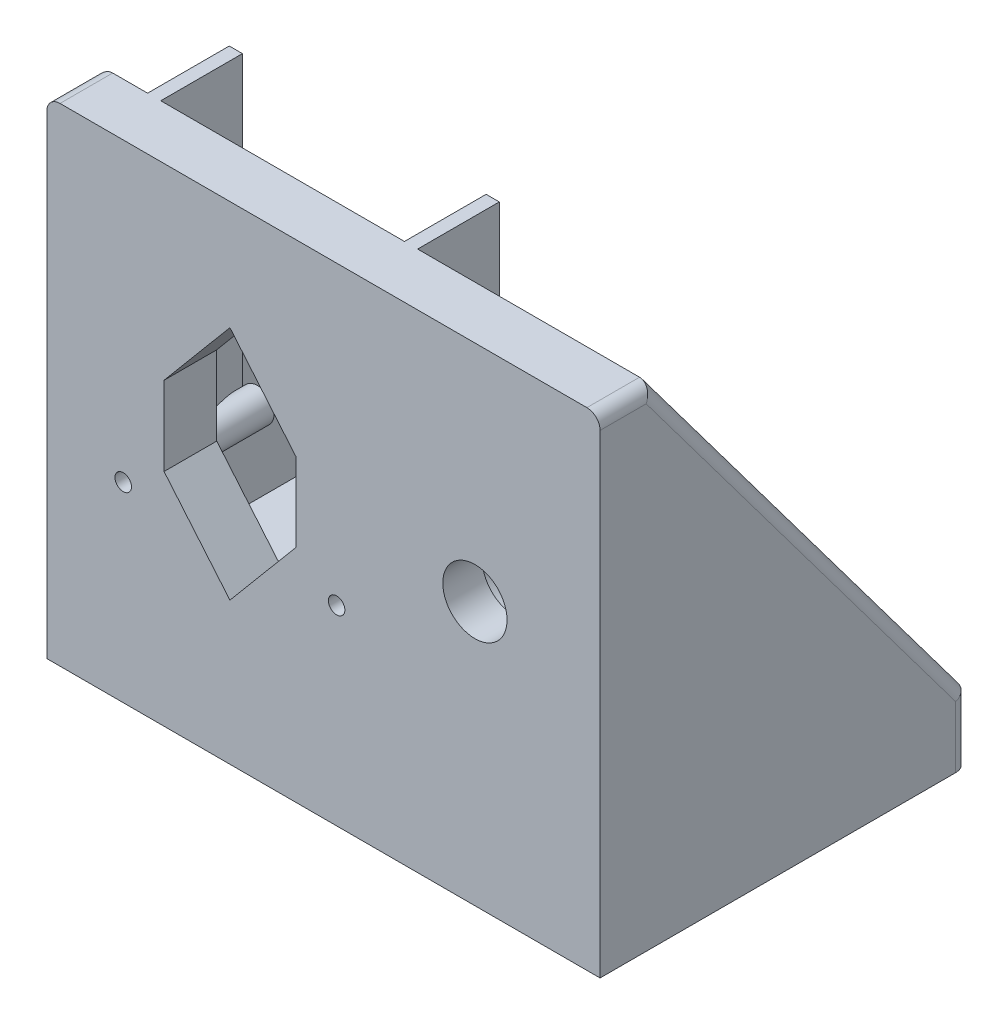
SolidWorks part; units mm, degrees
ref_plane "Front Plane" through (0, 0, 0) normal (0, 0, 1) x (1, 0, 0)
ref_plane "Top Plane" through (0, 0, 0) normal (0, 1, 0) x (1, 0, 0)
ref_plane "Right Plane" through (0, 0, 0) normal (1, 0, 0) x (0, 0, -1)
sketch "Sketch1" plane through (0, 0, 0) normal (0, 1, 0) x (1, 0, 0)
  line L1 (0, 0) -> (42, 0)
  line L2 (0, 0) -> (0, 28)
  line L3 (0, 28) -> (42, 28)
  line L4 (42, 0) -> (42, 28)
  dimension "D1" = 28
  dimension "D2" = 42
extrude "Boss-Extrude1" add sketch "Sketch1" along normal blind 5
sketch "Sketch2" plane through (0, 5, 0) normal (0, 1, 0) x (1, 0, 0)
  line L0 (42, 0) -> (42, 28) construction
  line L1 (0, 0) -> (42, 0)
  line L2 (0, 0) -> (0, 4)
  line L3 (0, 4) -> (42, 4)
  line L4 (42, 0) -> (42, 4)
  dimension "D1" = 4
extrude "Boss-Extrude2" add sketch "Sketch2" along normal blind 32
hole_wizard "Tap Drill for M1.6x0.35 Tap1" positions "Sketch3" profile "Sketch4" hole size "M1.6x0.35" standard "ANSI Metric" end condition through all
sketch "Sketch3" plane through (0, 0, -4) normal (0, 0, -1) x (-1, 0, 0)
  line L4 (0, 37) -> (0, 5) construction
  line L5 (-5.8, 14.5) -> (-22, 14.5) construction
  line L6 (-42, 37) -> (0, 37) construction
  point P0 (-22, 14.5)
  point P2 (-5.8, 14.5)
  dimension "D1" = 22.5
  dimension "D2" = 22
  dimension "D3" = 16.2
sketch "Sketch4" plane through (22, 14.5, -4) normal (1, 0, 0) x (0, 1, 0)
  line L0 (0, 0) -> (0, 4)
  line L1 (0, 4) -> (0.625, 4)
  line L2 (0.625, 4) -> (0.625, 0)
  line L5 (0.625, 0) -> (0, 0)
  line L11 (0, -6.35) -> (0, 107.95) construction
  dimension "Thru Hole Dia." = 1.25
  dimension "Thru Hole Depth" = 4
hole_wizard "M3 Clearance Hole1" positions "Sketch5" profile "Sketch6" hole size "M3" standard "ANSI Metric" end condition through all
sketch "Sketch5" plane through (0, 5, 0) normal (0, 1, 0) x (1, 0, 0)
  line L1 (15.5, 23) -> (30.5, 23) construction
  line L2 (15.5, 23) -> (15.5, 10) construction
  line L3 (15.5, 10) -> (30.5, 10) construction
  line L4 (30.5, 23) -> (30.5, 10) construction
  line L9 (23, 28) -> (23, 23) construction
  line L12 (30.5, 16.5) -> (38, 16.5) construction
  line L15 (0, 0) -> (42, 0) construction
  line L16 (42, 4) -> (42, 28) construction
  point P0 (15.5, 23)
  point P2 (30.5, 23)
  point P4 (30.5, 10)
  point P6 (15.5, 10)
  dimension "D1" = 15
  dimension "D2" = 13
  dimension "D3" = 23
  dimension "D4" = 11.5
sketch "Sketch6" plane through (15.5, 5, -23) normal (1, 0, 0) x (0, 0, 1)
  line L0 (0, 0) -> (0, 5)
  line L1 (0, 5) -> (1.7, 5)
  line L2 (1.7, 5) -> (1.7, 0)
  line L5 (1.7, 0) -> (0, 0)
  line L11 (0, -6.35) -> (0, 107.95) construction
  dimension "Thru Hole Dia." = 3.4
  dimension "Thru Hole Depth" = 5
sketch "Sketch7" plane through (0, 0, 0) normal (-1, 0, 0) x (0, 0, 1)
  line L0 (-28, 5) -> (-4, 37)
  line L1 (-4, 37) -> (-4, 5)
  line L2 (-4, 5) -> (-28, 5)
extrude "Boss-Extrude3" add sketch "Sketch7" against normal blind 2.5
sketch "Sketch8" plane through (42, 0, 0) normal (1, 0, 0) x (0, 0, -1)
  line L0 (28, 5) -> (4, 37)
  line L1 (4, 37) -> (4, 5)
  line L2 (4, 5) -> (28, 5)
extrude "Boss-Extrude4" add sketch "Sketch8" against normal blind 2.5
fillet "Fillet2" radius 1 8 edges at (39.5, 21, -16) (2.5, 21, -16) (42, 37, -2) (0, 37, -2) (0, 2.5, -28) (42, 2.5, -28) (42, 21, -16) (0, 21, -16)
sketch "Sketch9" plane through (0, 0, -4) normal (0, 0, -1) x (-1, 0, 0)
  line L0 (-42, 36) -> (-42, 0) construction
  line L3 (-39.5, 5) -> (-2.5, 5) construction
  circle A0 centre (-32.5, 20) radius 3.25
  dimension "D1" = 6.5
  dimension "D2" = 9.5
  dimension "D3" = 15
extrude "Cut-Extrude1" cut sketch "Sketch9" against normal blind 1
sketch "Sketch10" plane through (0, 0, -3) normal (0, 0, -1) x (-1, 0, 0)
  circle A0 centre (-32.5, 20) radius 2.44
  dimension "D1" = 4.88
extrude "Cut-Extrude2" cut sketch "Sketch10" against normal through all
sketch "Sketch11" plane through (0, 0, -4) normal (0, 0, -1) x (-1, 0, 0)
  line L0 (-22, 14.5) -> (-5.8, 14.5) construction
  line L1 (-13.9, 14.5) -> (-13.9, 37) construction
  line L2 (-40.5, 37) -> (-1.5, 37) construction
  line L3 (-3.65, 37) -> (-4.65, 37)
  line L8 (-24.15, 37) -> (-23.15, 37)
  line L9 (-24.15, 37) -> (-24.15, 14.0101)
  line L11 (-23.15, 37) -> (-23.15, 14.9899)
  line L12 (-3.65, 37) -> (-3.65, 14.0101)
  line L13 (-3.65, 14.0101) -> (-4.65, 14.0101)
  line L14 (-4.65, 37) -> (-4.65, 14.9899)
  line L15 (-24.15, 14.0101) -> (-23.15, 14.0101)
  arc A0 (-23.15, 14.0101) -> (-23.15, 14.9899) centre (-22, 14.5) ccw
  arc A1 (-4.65, 14.9899) -> (-4.65, 14.0101) centre (-5.8, 14.5) ccw
  circle A2 centre (-5.8, 14.5) radius 0.625 construction
  circle A3 centre (-5.8, 14.5) radius 0.625
  circle A4 centre (-22, 14.5) radius 0.625 construction
  circle A5 centre (-22, 14.5) radius 0.625
  point P25 (-24.15, 25.5051)
  dimension "D1" = 2.5
  dimension "D2" = 1
  dimension "D3" = 1
  dimension "D4" = 20.5
extrude "Boss-Extrude5" add sketch "Sketch11" along normal blind 6.2
sketch "Sketch12" plane through (0, 0, -4) normal (0, 0, -1) x (-1, 0, 0)
  line L0 (-5.8, 14.5) -> (-22, 14.5) construction
  line L1 (-11.4, 18) -> (-16.4, 18)
  line L2 (-11.4, 18) -> (-11.4, 21.5)
  line L3 (-11.4, 21.5) -> (-16.4, 21.5)
  line L4 (-16.4, 18) -> (-16.4, 21.5)
  line L5 (-13.9, 14.5) -> (-13.9, 18) construction
  circle A0 centre (-5.8, 14.5) radius 0.625 construction
  dimension "D1" = 3.5
  dimension "D2" = 5
  dimension "D3" = 3.5
sketch "Sketch13" plane through (0, 0, -4) normal (0, 0, -1) x (-1, 0, 0)
  line L1 (-13.9, 28.7088) -> (-8.9, 22.75)
  line L3 (-13.9, 14.5) -> (-13.9, 28.7088) construction
  line L4 (-8.9, 22.75) -> (-8.9, 16.75)
  line L5 (-8.9, 16.75) -> (-13.9, 10.7912)
  line L6 (-13.9, 10.7912) -> (-18.9, 16.75)
  line L7 (-18.9, 16.75) -> (-18.9, 22.75)
  line L8 (-11.4, 18) -> (-11.4, 21.5) construction
  line L9 (-11.4, 18) -> (-11.4, 21.5) construction
  line L10 (-8.9, 19.75) -> (-11.4, 19.75) construction
  line L11 (-8.9, 16.75) -> (-18.9, 16.75) construction
  line L12 (-18.9, 22.75) -> (-13.9, 28.7088)
  line L13 (-8.9, 22.75) -> (-18.9, 22.75) construction
  dimension "D1" = 40
  dimension "D2" = 6
  dimension "D3" = 10
extrude "Cut-Extrude3" cut sketch "Sketch13" against normal through all
sketch "Sketch14" plane through (0, 37, 0) normal (0, 1, 0) x (1, 0, 0)
  line L0 (23.15, 10.2) -> (21.15, 4)
  line L1 (23.15, 4) -> (4.65, 4) construction
  line L2 (21.15, 4) -> (23.15, 4)
  line L3 (23.15, 4) -> (23.15, 10.2)
  line L4 (4.65, 10.2) -> (6.65, 4)
  line L5 (6.65, 4) -> (4.65, 4)
  line L6 (4.65, 4) -> (4.65, 10.2)
  dimension "D1" = 2
extrude "Boss-Extrude6" add sketch "Sketch14" against normal up to next
sketch "Sketch16" plane through (0, 0, -4) normal (0, 0, -1) x (-1, 0, 0)
  line L0 (-29.25, 20) -> (-27.75, 20) construction
  circle A0 centre (-32.5, 20) radius 4.75
  circle A1 centre (-32.5, 20) radius 3.25 construction
  circle A2 centre (-32.5, 20) radius 3.25
  dimension "D1" = 1.5
extrude "Boss-Extrude8" add sketch "Sketch16" along normal blind 7
ref_plane "Plane1" through (0, 24.75, 0) normal (0, 1, 0) x (1, 0, 0)
sketch "Sketch17" plane through (0, 24.75, 0) normal (0, 1, 0) x (1, 0, 0)
  line L0 (37.25, 4) -> (37.25, 11) construction
  line L1 (27.75, 11) -> (27.75, 4) construction
  line L2 (37.25, 4) -> (37.25, 11) construction
  line L3 (27.75, 11) -> (27.75, 4) construction
  line L4 (37.25, 4) -> (27.75, 4) construction
  line L5 (37.25, 4) -> (27.75, 4) construction
  line L6 (37.25, 11) -> (27.75, 11) construction
  line L7 (37.25, 11) -> (27.75, 11) construction
  line L8 (32.5, 11) -> (32.5, 4) construction
  circle A0 centre (32.5, 8.1) radius 1.5
  dimension "D1" = 3
  dimension "D2" = 4.1
extrude "Cut-Extrude4" cut sketch "Sketch17" against normal blind 0.5
hole_wizard "Tap Drill for M1.6x0.35 Tap2" positions "Sketch18" profile "Sketch19" hole size "M1.6x0.35" standard "ANSI Metric" end condition up to next
sketch "Sketch18" plane through (0, 24.25, 0) normal (0, 1, 0) x (1, 0, 0)
  circle A0 centre (32.5, 8.1) radius 1.5 construction
  point P0 (32.5, 8.1)
sketch "Sketch19" plane through (32.5, 24.25, -8.1) normal (1, 0, 0) x (0, 0, 1)
  line L0 (0, 0) -> (0, 1)
  line L1 (0, 1) -> (0.625, 1)
  line L2 (0.625, 1) -> (0.625, 0)
  line L5 (0.625, 0) -> (0, 0)
  line L11 (0, -6.35) -> (0, 107.95) construction
  dimension "Thru Hole Dia." = 1.25
  dimension "Thru Hole Depth" = 1
sketch "Sketch21" plane through (0, 0, -10.2) normal (0, 0, -1) x (-1, 0, 0)
  line L0 (-6.65, 15.4165) -> (-6.65, 37) construction
  line L1 (-4.65, 37) -> (-6.65, 37)
  line L2 (-4.65, 37) -> (-4.65, 29)
  line L3 (-4.65, 29) -> (-6.65, 29)
  line L4 (-6.65, 37) -> (-6.65, 29)
  line L5 (-6.65, 15.4165) -> (-6.65, 37) construction
  line L6 (-6.2816, 29) -> (-21.15, 29) construction
  line L7 (-23.15, 37) -> (-21.15, 37)
  line L8 (-23.15, 37) -> (-23.15, 29)
  line L9 (-23.15, 29) -> (-21.15, 29)
  line L10 (-21.15, 37) -> (-21.15, 29)
  line L11 (-21.15, 15.4165) -> (-21.15, 37) construction
  line L12 (-21.15, 15.4165) -> (-21.15, 37) construction
  dimension "D1" = 8
extrude "Cut-Extrude5" cut sketch "Sketch21" against normal up to surface (6.2 mm away) up to face at (16.5625, 24.2349, -4)
